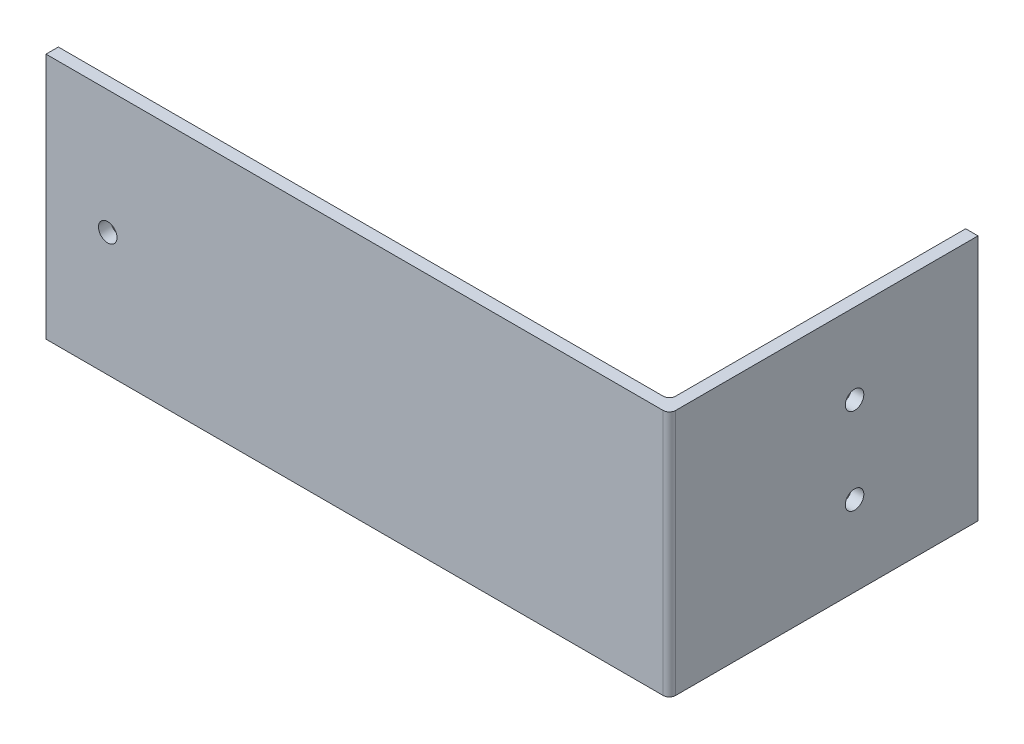
SolidWorks part; units mm, degrees
ref_plane "Front Plane" through (0, 0, 0) normal (0, 0, 1) x (1, 0, 0)
ref_plane "Top Plane" through (0, 0, 0) normal (0, 1, 0) x (1, 0, 0)
ref_plane "Right Plane" through (0, 0, 0) normal (1, 0, 0) x (0, 0, -1)
sketch "Sketch1" plane through (0, 0, 0) normal (0, 0, 1) x (1, 0, 0)
  line L1 (0, 0) -> (100, 0)
  line L2 (0, 0) -> (0, 40)
  line L3 (0, 40) -> (100, 40)
  line L4 (100, 0) -> (100, 40)
  circle A0 centre (10, 20) radius 1.5
  dimension "D3" = 20
  dimension "D4" = 10
  dimension "D1" = 40
  dimension "D2" = 100
extrude "Boss-Extrude1" add sketch "Sketch1" along normal blind 2
sketch "Sketch2" plane through (0, 0, 2) normal (0, 0, 1) x (1, 0, 0)
  line L0 (0, 0) -> (100, 0) construction
  line L1 (100, 40) -> (101, 40)
  line L2 (100, 40) -> (100, 0)
  line L3 (100, 0) -> (101, 0)
  line L4 (101, 40) -> (101, 0)
  line L5 (100, 40) -> (99, 40)
  line L6 (100, 40) -> (100, 0)
  line L7 (100, 0) -> (99, 0)
  line L8 (99, 40) -> (99, 0)
  line M2 (0, 0) -> (100, 0)
  line M3 (100, 0) -> (100, 40)
  line M4 (100, 40) -> (0, 40)
  dimension "D1" = 1
  dimension "D2" = 1
extrude "Boss-Extrude3" add sketch "Sketch2" against normal blind 50 contours L4 L1 L3 M3 | L8 M4 M2 M3 region at (100.5, 20, 2) region at (99.5, 20, 2)
fillet "Fillet2" radius 1 2 edges at (101, 20, 2) (99, 20, 0)
sketch "Sketch3" plane through (101, 0, 0) normal (1, 0, 0) x (0, 0, -1)
  line L0 (48, 20) -> (28, 20)
  line L1 (48, 40) -> (48, 0) construction
  line L2 (28, 20) -> (28, 13)
  line L3 (28, 20) -> (28, 27)
  circle A0 centre (28, 13) radius 1.5
  circle A1 centre (28, 27) radius 1.5
  dimension "D1" = 7
  dimension "D2" = 7
extrude "Cut-Extrude1" cut sketch "Sketch3" against normal blind 10 contours A1 | A0 region at (101, 14.0307, -29.0307) region at (101, 28.0307, -26.9693)
